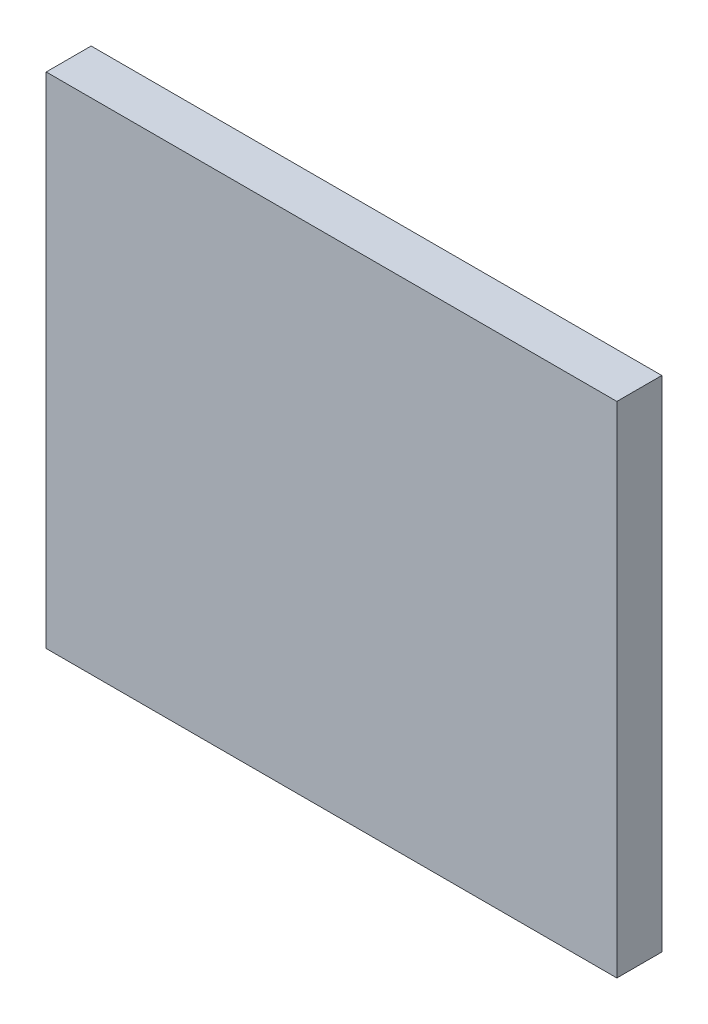
SolidWorks part; units mm, degrees
ref_plane "Front Plane" through (0, 0, 0) normal (0, 0, 1) x (1, 0, 0)
ref_plane "Top Plane" through (0, 0, 0) normal (0, 1, 0) x (1, 0, 0)
ref_plane "Right Plane" through (0, 0, 0) normal (1, 0, 0) x (0, 0, -1)
sketch "Sketch1" plane through (0, 0, 0) normal (0, 0, 1) x (1, 0, 0)
  line L0 (-10.16, 8.89) -> (-10.16, -8.89)
  line L1 (-10.16, -8.89) -> (10.16, -8.89)
  line L2 (10.16, -8.89) -> (10.16, 8.89)
  line L3 (10.16, 8.89) -> (-10.16, 8.89)
  line L5 (0, 8.89) -> (0, -8.89) construction
  line L6 (-10.16, 0) -> (10.16, 0) construction
  line L7 (55, 0) -> (-55, 0) construction
  line L8 (0, -55) -> (0, 55) construction
  dimension "D1" = 20.32
  dimension "D2" = 17.78
extrude "Boss-Extrude1" add sketch "Sketch1" along normal blind 1.6
sketch "Sketch2" plane through (0, 0, 0) normal (0, 0, 1) x (1, 0, 0)
  line L0 (5.2705, 3.683) -> (5.2705, -3.683)
  line L1 (5.2705, -3.683) -> (-5.2705, -3.683)
  line L2 (-5.2705, -3.683) -> (-5.2705, 3.683)
  line L3 (-5.2705, 3.683) -> (5.2705, 3.683)
  line L4 (5.2705, 0) -> (-5.2705, 0) construction
  line L5 (0, 3.683) -> (0, -3.683) construction
  dimension "D1" = 7.366
  dimension "D2" = 10.541
extrude "Boss-Extrude2" add sketch "Sketch2" against normal blind 3.556
sketch "Sketch3" plane through (0, 3.683, 0) normal (0, 1, 0) x (1, 0, 0)
  line L0 (0, 0) -> (0, 3.556) construction
  line L4 (-5.2705, 0) -> (5.2705, 0)
  line L5 (5.2705, 0) -> (5.2705, 3.556)
  line L6 (5.2705, 3.556) -> (-5.2705, 3.556)
  line L7 (-5.2705, 3.556) -> (-5.2705, 0)
  line L8 (-5.2705, 0) -> (5.2705, 0) construction
  line L9 (5.2705, 0) -> (5.2705, 3.556) construction
  line L10 (5.2705, 3.556) -> (-5.2705, 3.556) construction
  line L11 (-5.2705, 3.556) -> (-5.2705, 0) construction
  point P6 (0, 1.778)
  dimension "D1" = 0
ref_axis "Axis1" through (0, -10.2459, -1.778) along (0, 1, 0)
